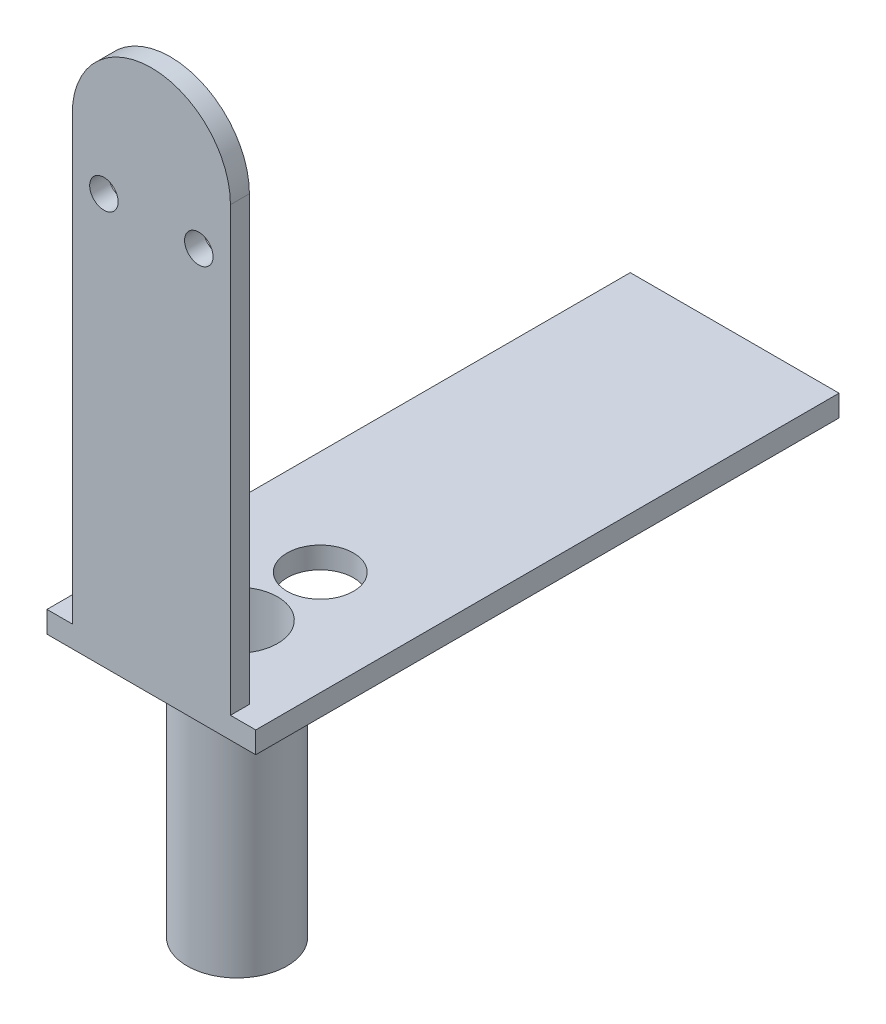
SolidWorks part; units mm, degrees
ref_plane "Front Plane" through (0, 0, 0) normal (0, 0, 1) x (1, 0, 0)
ref_plane "Top Plane" through (0, 0, 0) normal (0, 1, 0) x (1, 0, 0)
ref_plane "Right Plane" through (0, 0, 0) normal (1, 0, 0) x (0, 0, -1)
sketch "Sketch1" plane through (0, 0, 0) normal (0, 0, 1) x (1, 0, 0)
  line L0 (0, 0) -> (33, 0)
  line L1 (16.5, 0) -> (29, 0)
  line L2 (16.5, 0) -> (16.5, 9.4766)
  line L3 (4, 0) -> (4, 80.5)
  line L4 (29, 0) -> (29, 80.5)
  line L5 (0, 0) -> (0, 80.5)
  line L6 (0, 80.5) -> (4, 80.5)
  line L7 (33, 0) -> (33, 80.5)
  line L8 (33, 80.5) -> (29, 80.5)
  arc A0 (33, 80.5) -> (0, 80.5) centre (16.5, 80.5) ccw
  arc A1 (4, 80.5) -> (29, 80.5) centre (16.5, 80.5) cw
  point P5 (4, 0)
  dimension "D1" = 33
  dimension "D2" = 12.5
  dimension "D3" = 80.5
extrude "Boss-Extrude1" add sketch "Sketch1" along normal blind 71 contours L6 L5 L0 L3 | L6 A1 L8 A0 | L7 L8 L4 L0 region at (2, 40.25, 0) region at (16.5, 96.631, 0) region at (31, 40.25, 0)
sketch "Sketch2" plane through (0, 0, 71) normal (0, 0, 1) x (1, 0, 0)
  line L2 (33, 48.5) -> (0, 48.5)
  line L3 (0, 0) -> (0, 80.5) construction
  line L4 (0, 48.5) -> (0, 80.5)
  line L5 (33, 0) -> (33, 80.5) construction
  line L6 (33, 48.5) -> (33, 80.5)
  arc A0 (33, 80.5) -> (0, 80.5) centre (16.5, 80.5) ccw construction
  arc A1 (33, 80.5) -> (0, 80.5) centre (16.5, 80.5) ccw
  point P8 (16.5, 48.5)
extrude "Boss-Extrude2" add sketch "Sketch2" against normal blind 4
sketch "Sketch3" plane through (0, 0, 67) normal (0, 0, -1) x (-1, 0, 0)
  line L0 (-4, 48.5) -> (-29, 48.5) construction
  line L1 (-4, 48.5) -> (-29, 48.5)
  line L3 (-29, 44.5) -> (-4, 44.5)
  line L5 (0, 0) -> (0, 80.5) construction
  line L6 (0, 0) -> (0, 48.5)
  line L7 (-4, 48.5) -> (0, 48.5)
  line L8 (0, 0) -> (-3.8379, 0)
  line L9 (-4, 44.5) -> (-3.8379, 0)
  line L10 (-16.5, 44.5) -> (-16.5, 41.0104)
  line L11 (-33, 0) -> (-33, 48.5)
  line L12 (-29, 48.5) -> (-33, 48.5)
  line L13 (-29, 44.5) -> (-29.1621, 0)
  line L14 (-33, 0) -> (-29.1621, 0)
  line M8 (-29, 48.5) -> (-4, 48.5)
extrude "Boss-Extrude3" add sketch "Sketch3" against normal blind 34.2 contours L11 L14 L13 L3 L9 L8 L6 L7 L12 M8 region at (2, 47.9134, 67)
sketch "Sketch4" plane through (0, 0, 0) normal (0, 0, -1) x (-1, 0, 0)
  line L6 (-4, 80.5) -> (-4, 0)
  line L7 (-4, 0) -> (0, 0)
  line L8 (0, 0) -> (0, 80.5)
  line L9 (-33, 80.5) -> (-33, 0)
  line L10 (-33, 0) -> (-29, 0)
  line L11 (-29, 0) -> (-29, 80.5)
  line L12 (-4, 80.5) -> (-4, 0)
  line L13 (-4, 0) -> (0, 0)
  line L14 (0, 0) -> (0, 80.5)
  line L15 (-33, 80.5) -> (-33, 0)
  line L16 (-33, 0) -> (-29, 0)
  line L17 (-29, 0) -> (-29, 80.5)
  arc A2 (0, 80.5) -> (-33, 80.5) centre (-16.5, 80.5) ccw
  arc A3 (-4, 80.5) -> (-29, 80.5) centre (-16.5, 80.5) ccw
  arc A4 (0, 80.5) -> (-33, 80.5) centre (-16.5, 80.5) ccw
  arc A5 (-4, 80.5) -> (-29, 80.5) centre (-16.5, 80.5) ccw
  dimension "D1" = 0
extrude "Cut-Extrude1" cut sketch "Sketch4" against normal blind 13
sketch "Sketch5" plane through (0, 0, 71) normal (0, 0, 1) x (1, 0, 0)
  line L0 (0, 80.5) -> (33, 80.5)
  circle A0 centre (16.5, 80.5) radius 10
  dimension "D1" = 20
extrude "Cut-Extrude2" cut sketch "Sketch5" against normal blind 13 contours L0 A0 | L0 A0 region at (16.5, 84.7441, 71) region at (16.5, 76.2559, 71)
sketch "Sketch6" plane through (0, 0, 71) normal (0, 0, 1) x (1, 0, 0)
  line L0 (16.5, 70.5) -> (16.5, 73.1374)
  line L1 (16.5, 70.5) -> (33, 70.5)
  line L2 (33, 48.5) -> (33, 80.5) construction
  circle A0 centre (26.5, 70.5) radius 1.7
  circle A1 centre (6.5, 70.5) radius 1.7
  dimension "D2" = 3.4
  dimension "D1" = 6.5
extrude "Cut-Extrude3" cut sketch "Sketch6" against normal blind 13 contours A1 | L1 A0 | L1 A0 region at (26.5, 71.2215, 71) region at (26.5, 69.7785, 71) region at (6.5, 70.5, 71)
sketch "Sketch7" plane through (0, 0, 71) normal (0, 0, 1) x (1, 0, 0)
  circle A0 centre (6.5, 70.5) radius 3.25
  circle A1 centre (26.5, 70.5) radius 3.25
  dimension "D1" = 6.5
extrude "Cut-Extrude4" cut sketch "Sketch7" against normal blind 2.5
sketch "Sketch9" plane through (0, 0, 0) normal (0, -1, 0) x (1, 0, 0)
  line L0 (29.1621, 101.2) -> (29.1621, 71) construction
  line L1 (29.1621, 101.2) -> (29.1621, 71)
  line L2 (29.1621, 71) -> (29, 71)
  line L3 (29, 71) -> (29, 120)
  line L4 (29, 120) -> (29.1621, 101.2)
  line L6 (29, 67) -> (4, 67) construction
  line L7 (29, 67) -> (4, 67)
  line L8 (16.5, 67) -> (16.5, 71)
  line L9 (4, 120) -> (3.8379, 101.2)
  line L10 (4, 71) -> (4, 120)
  line L11 (3.8379, 71) -> (4, 71)
  line L12 (3.8379, 101.2) -> (3.8379, 71)
extrude "Boss-Extrude4" add sketch "Sketch9" against normal up to surface (44.5 mm away) contours L4 L1 L2 L3 | L9 L12 L11 L10 up to face at (16.5, 44.5, 79.7333)
sketch "Sketch10" plane through (0, 0, 101.2) normal (0, 0, 1) x (1, 0, 0)
  line L1 (40.2439, -6.5645) -> (-5.7585, -6.5645)
  line L2 (40.2439, -6.5645) -> (40.2439, 55.1467)
  line L3 (40.2439, 55.1467) -> (-5.7585, 55.1467)
  line L4 (-5.7585, -6.5645) -> (-5.7585, 55.1467)
  line L5 (40.2439, -6.5645) -> (-5.7585, 55.1467) construction
  line L6 (40.2439, 55.1467) -> (-5.7585, -6.5645) construction
  point P0 (17.2427, 24.2911)
extrude "Cut-Extrude5" cut sketch "Sketch10" along normal blind 42
fillet "Fillet1" radius 18 2 edges at (16.5, 44.5, 67) (16.5, 48.5, 71)
sketch "Sketch11" plane through (0, 0, 101.2) normal (0, 0, 1) x (1, 0, 0)
  line L0 (29, 0) -> (4, 0)
  line L8 (4, 44.5) -> (29, 44.5)
  line L9 (29, 44.5) -> (29, 0)
  line L10 (29, 0) -> (33, 0)
  line L11 (33, 0) -> (33, 48.5)
  line L12 (33, 48.5) -> (0, 48.5)
  line L13 (0, 48.5) -> (0, 0)
  line L14 (0, 0) -> (4, 0)
  line L15 (4, 0) -> (4, 44.5)
  line L18 (29, 0) -> (33, 0)
  line L19 (33, 0) -> (33, 48.5)
  line L20 (33, 48.5) -> (0, 48.5)
  line L21 (0, 48.5) -> (0, 0)
  line L22 (0, 0) -> (4, 0)
  dimension "D1" = 0
extrude "Boss-Extrude5" add sketch "Sketch11" along normal blind 4
fillet "Fillet3" radius 16.2 1 edges at (16.5, 48.5, 105.2)
fillet "Fillet4" radius 14 1 edges at (16.5, 44.5, 101.2)
sketch "Sketch12" plane through (0, 0, 0) normal (0, -1, 0) x (1, 0, 0)
  line L8 (4, 13) -> (4, 101.2)
  line L9 (4, 101.2) -> (29, 101.2)
  line L10 (29, 101.2) -> (29, 13)
  line L11 (29, 13) -> (33, 13)
  line L12 (33, 13) -> (33, 105.2)
  line L13 (33, 105.2) -> (0, 105.2)
  line L14 (0, 105.2) -> (0, 13)
  line L15 (0, 13) -> (4, 13)
  line L16 (4, 13) -> (4, 101.2)
  line L17 (4, 101.2) -> (29, 101.2)
  line L18 (29, 101.2) -> (29, 13)
  line L19 (29, 13) -> (33, 13)
  line L20 (33, 13) -> (33, 105.2)
  line L21 (33, 105.2) -> (0, 105.2)
  line L22 (0, 105.2) -> (0, 13)
  line L23 (0, 13) -> (4, 13)
  dimension "D1" = 0
extrude "Cut-Extrude6" cut sketch "Sketch12" against normal blind 10.6
sketch "Sketch13" plane through (0, 0, 13) normal (0, 0, -1) x (-1, 0, 0)
  line L6 (-33, 80.5) -> (-33, 10.6)
  line L7 (-33, 10.6) -> (-29, 10.6)
  line L8 (-29, 10.6) -> (-29, 80.5)
  line L9 (-4, 80.5) -> (-4, 10.6)
  line L10 (-4, 10.6) -> (0, 10.6)
  line L11 (0, 10.6) -> (0, 80.5)
  line L12 (-33, 80.5) -> (-33, 10.6)
  line L13 (-33, 10.6) -> (-29, 10.6)
  line L14 (-29, 10.6) -> (-29, 80.5)
  line L15 (-4, 80.5) -> (-4, 10.6)
  line L16 (-4, 10.6) -> (0, 10.6)
  line L17 (0, 10.6) -> (0, 80.5)
  arc A2 (-4, 80.5) -> (-29, 80.5) centre (-16.5, 80.5) ccw
  arc A3 (0, 80.5) -> (-33, 80.5) centre (-16.5, 80.5) ccw
  arc A4 (-4, 80.5) -> (-29, 80.5) centre (-16.5, 80.5) ccw
  arc A5 (0, 80.5) -> (-33, 80.5) centre (-16.5, 80.5) ccw
  dimension "D1" = 0
extrude "Boss-Extrude6" add sketch "Sketch13" along normal blind 4
ref_plane "Plane1" through (0, 0, 13) normal (0, 0, -1) x (-1, 0, 0)
sketch "Sketch14" plane through (0, 0, 13) normal (0, 0, -1) x (-1, 0, 0)
  line L0 (-29, 10.6) -> (-4, 10.6)
  line L6 (-33, 80.5) -> (-33, 10.6)
  line L7 (-33, 10.6) -> (-29, 10.6)
  line L8 (-29, 10.6) -> (-29, 80.5)
  line L9 (-4, 80.5) -> (-4, 10.6)
  line L10 (-4, 10.6) -> (0, 10.6)
  line L11 (0, 10.6) -> (0, 80.5)
  line L12 (-33, 80.5) -> (-33, 10.6)
  line L13 (-33, 10.6) -> (-29, 10.6)
  line L16 (-4, 10.6) -> (0, 10.6)
  line L17 (0, 10.6) -> (0, 80.5)
  arc A2 (0, 80.5) -> (-33, 80.5) centre (-16.5, 80.5) ccw
  arc A3 (-4, 80.5) -> (-29, 80.5) centre (-16.5, 80.5) ccw
  arc A4 (0, 80.5) -> (-33, 80.5) centre (-16.5, 80.5) ccw
  dimension "D1" = 0
extrude "Cut-Extrude7" cut sketch "Sketch14" against normal blind 148
sketch "Sketch15" plane through (0, 0, 13) normal (0, 0, 1) x (1, 0, 0)
  line L0 (4, 10.6) -> (29, 10.6)
  line L6 (29, 80.5) -> (29, 10.6)
  line L7 (29, 10.6) -> (33, 10.6)
  line L8 (33, 10.6) -> (33, 80.5)
  line L9 (0, 80.5) -> (0, 10.6)
  line L10 (0, 10.6) -> (4, 10.6)
  line L11 (4, 10.6) -> (4, 80.5)
  line L12 (29, 80.5) -> (29, 10.6)
  line L13 (29, 10.6) -> (33, 10.6)
  line L17 (4, 10.6) -> (4, 80.5)
  arc A2 (33, 80.5) -> (0, 80.5) centre (16.5, 80.5) ccw
  arc A3 (29, 80.5) -> (4, 80.5) centre (16.5, 80.5) ccw
  arc A5 (29, 80.5) -> (4, 80.5) centre (16.5, 80.5) ccw
  line M10 (29, 80.5) -> (29, 10.6)
  line M16 (4, 10.6) -> (4, 80.5)
  arc M17 (4, 80.5) -> (29, 80.5) centre (16.5, 80.5) cw
  dimension "D1" = 0
extrude "Boss-Extrude7" add sketch "Sketch15" along normal blind 3 separate body contours L0 M16 M10 M17 region at (16.5, 50.5076, 13)
sketch "Sketch16" plane through (0, 0, 9) normal (0, 0, -1) x (-1, 0, 0)
  line L6 (-33, 80.5) -> (-33, 10.6)
  line L7 (-33, 10.6) -> (-29, 10.6)
  line L8 (-29, 10.6) -> (-29, 80.5)
  line L9 (-4, 80.5) -> (-4, 10.6)
  line L10 (-4, 10.6) -> (0, 10.6)
  line L11 (0, 10.6) -> (0, 80.5)
  line L12 (-33, 80.5) -> (-33, 10.6)
  line L13 (-33, 10.6) -> (-29, 10.6)
  line L14 (-29, 10.6) -> (-29, 80.5)
  line L15 (-4, 80.5) -> (-4, 10.6)
  line L16 (-4, 10.6) -> (0, 10.6)
  line L17 (0, 10.6) -> (0, 80.5)
  arc A2 (0, 80.5) -> (-33, 80.5) centre (-16.5, 80.5) ccw
  arc A3 (-4, 80.5) -> (-29, 80.5) centre (-16.5, 80.5) ccw
  arc A4 (0, 80.5) -> (-33, 80.5) centre (-16.5, 80.5) ccw
  arc A5 (-4, 80.5) -> (-29, 80.5) centre (-16.5, 80.5) ccw
  dimension "D1" = 0
extrude "Cut-Extrude8" cut sketch "Sketch16" against normal blind 14
sketch "Sketch17" plane through (0, 0, 13) normal (0, 0, -1) x (-1, 0, 0)
  line L0 (-16.5, 93) -> (-16.5, 68)
  line L1 (-16.5, 68) -> (-4, 68)
  line L2 (-4, 10.6) -> (-4, 80.5) construction
  arc A0 (-4, 80.5) -> (-29, 80.5) centre (-16.5, 80.5) ccw construction
  circle A1 centre (-9, 72) radius 2.25
  circle A2 centre (-24, 72) radius 2.25
  dimension "D2" = 4.5
  dimension "D3" = 5
  dimension "D4" = 4
  dimension "D1" = 25
extrude "Cut-Extrude9" cut sketch "Sketch17" against normal blind 14 contours A2 | A1 region at (24, 72, 13)
sketch "Sketch18" plane through (0, 10.6, 0) normal (0, -1, 0) x (1, 0, 0)
  line L0 (29, 16) -> (29, -76.2)
  line L1 (29, 16) -> (4, 16)
  line L2 (4, 16) -> (4, -76.2)
  line L3 (4, -76.2) -> (29, -76.2)
  dimension "D1" = 92.2
extrude "Boss-Extrude8" add sketch "Sketch18" along normal blind 4
sketch "Sketch19" plane through (0, 6.6, 0) normal (0, -1, 0) x (1, 0, 0)
  line L0 (4, 16) -> (0, 16)
  line L1 (0, 16) -> (0, -76.2)
  line L2 (4, -76.2) -> (0, -76.2)
  line L3 (4, -76.2) -> (4, 16)
  line L4 (16.5, 16) -> (16.5, 9.1971)
  line L5 (29, 16) -> (4, 16) construction
  line L6 (29, -76.2) -> (33, -76.2)
  line L7 (33, 16) -> (33, -76.2)
  line L8 (29, 16) -> (33, 16)
  line L9 (29, -76.2) -> (29, 16)
  line M7 (4, 16) -> (4, -76.2)
  line M9 (29, -76.2) -> (29, 16)
extrude "Boss-Extrude9" add sketch "Sketch19" against normal up to surface (4 mm away) contours L2 L0 L1 M7 | L8 L6 L7 M9 region at (2, 6.6, -30.1) region at (31, 6.6, -30.1) up to face at (16.5, 10.6, -31.6)
sketch "Sketch20" plane through (0, 6.6, 0) normal (0, -1, 0) x (1, 0, 0)
  line L0 (16.5, 16) -> (16.5, -10.7)
  line L1 (33, 16) -> (0, 16) construction
  circle A0 centre (16.5, -10.7) radius 5.25
  dimension "D2" = 10.5
  dimension "D1" = 26.7
extrude "Cut-Extrude10" cut sketch "Sketch20" against normal up to surface (4 mm away) contours A0 region at (12.8927, 6.6, -14.3073) up to face at (16.5, 10.6, -7.8)
sketch "Sketch21" plane through (0, 6.6, 0) normal (0, -1, 0) x (1, 0, 0)
  line L4 (33, 16) -> (0, 16)
  line L5 (0, 16) -> (0, -76.2)
  line L6 (0, -76.2) -> (33, -76.2)
  line L7 (33, -76.2) -> (33, 16)
  line L8 (33, 16) -> (0, 16)
  line L9 (0, 16) -> (0, -76.2)
  line L10 (0, -76.2) -> (33, -76.2)
  line L11 (33, -76.2) -> (33, 16)
  dimension "D1" = 0
extrude "Cut-Extrude11" cut sketch "Sketch21" against normal blind 0.6
sketch "Sketch22" plane through (0, 7.2, 0) normal (0, -1, 0) x (1, 0, 0)
  line L0 (16.5, 16) -> (16.5, 1.3)
  line L1 (33, 16) -> (0, 16) construction
  circle A0 centre (16.5, 1.3) radius 5.25
  dimension "D2" = 10.5
  dimension "D1" = 14.7
extrude "Cut-Extrude12" cut sketch "Sketch22" against normal up to surface (3.4 mm away) contours A0 region at (12.8927, 7.2, -2.3073) up to face at (16.5, 10.6, -15.95)
sketch "Sketch23" plane through (0, 7.2, 0) normal (0, -1, 0) x (1, 0, 0)
  line L0 (16.5, -5.45) -> (16.5, 10.35)
  circle A0 centre (16.5, -10.7) radius 5.25 construction
  circle A1 centre (16.5, 2.45) radius 7.9
  circle A2 centre (16.5, 2.45) radius 6.4
  dimension "D1" = 15.8
extrude "Boss-Extrude10" add sketch "Sketch23" along normal blind 40 contours A2 L0 A1 | A2 L0 A1 region at (8.7766, 7.2, 2.45) region at (16.6766, 7.2, -4.7)
sketch "Sketch24" plane through (0, 7.2, 0) normal (0, -1, 0) x (1, 0, 0)
  circle A2 centre (16.5, 2.45) radius 6.4 construction
  circle A3 centre (16.5, 2.45) radius 6.4
extrude "Cut-Extrude13" cut sketch "Sketch24" against normal up to surface (3.4 mm away) up to face at (16.5, 10.6, -3.95)
sketch "Sketch25" plane through (0, 10.6, 0) normal (0, 1, 0) x (1, 0, 0)
  line L0 (16.5, 76.2) -> (16.5, 74.7)
  line L1 (0, 76.2) -> (33, 76.2) construction
  line L2 (16.5, 74.7) -> (6.5, 74.7)
  line L3 (6.5, 74.7) -> (6.5, 72.7)
  line L4 (16.5, 74.7) -> (26.5, 74.7)
  line L5 (26.5, 74.7) -> (26.5, 72.7)
  line L6 (26.5, 72.7) -> (6.5, 72.7)
extrude "Boss-Extrude11" add sketch "Sketch25" along normal blind 15 contours L6 L5 L4 L2 L3 region at (16.5, 10.6, -73.7)
sketch "Sketch26" plane through (0, 10.6, 0) normal (0, 1, 0) x (1, 0, 0)
  line L0 (21.5, 74.7) -> (11.5, 74.7)
  line L1 (6.5, 74.7) -> (26.5, 74.7) construction
  line L2 (11.5, 74.7) -> (16.5, 74.7)
  line L3 (11.5, 74.7) -> (11.5, 76.2)
  line L4 (0, 76.2) -> (33, 76.2) construction
  line L5 (11.5, 76.2) -> (21.5, 76.2)
  line L6 (21.5, 76.2) -> (21.5, 74.7)
  point P5 (16.5, 74.7)
  dimension "D1" = 10
extrude "Boss-Extrude12" add sketch "Sketch26" along normal up to surface (15 mm away) contours L3 L5 L6 L0 up to face at (16.5, 25.6, -73.7)
sketch "Sketch27" plane through (0, 10.6, 0) normal (0, 1, 0) x (1, 0, 0)
  line L8 (6.5, 72.7) -> (26.5, 72.7)
  line L9 (26.5, 72.7) -> (26.5, 74.7)
  line L10 (26.5, 74.7) -> (21.5, 74.7)
  line L11 (21.5, 74.7) -> (21.5, 76.2)
  line L12 (21.5, 76.2) -> (11.5, 76.2)
  line L13 (11.5, 76.2) -> (11.5, 74.7)
  line L14 (11.5, 74.7) -> (6.5, 74.7)
  line L15 (6.5, 74.7) -> (6.5, 72.7)
  line L16 (6.5, 72.7) -> (26.5, 72.7)
  line L17 (26.5, 72.7) -> (26.5, 74.7)
  line L18 (26.5, 74.7) -> (21.5, 74.7)
  line L19 (21.5, 74.7) -> (21.5, 76.2)
  line L20 (21.5, 76.2) -> (11.5, 76.2)
  line L21 (11.5, 76.2) -> (11.5, 74.7)
  line L22 (11.5, 74.7) -> (6.5, 74.7)
  line L23 (6.5, 74.7) -> (6.5, 72.7)
  dimension "D1" = 0
extrude "Cut-Extrude14" cut sketch "Sketch27" along normal blind 36
